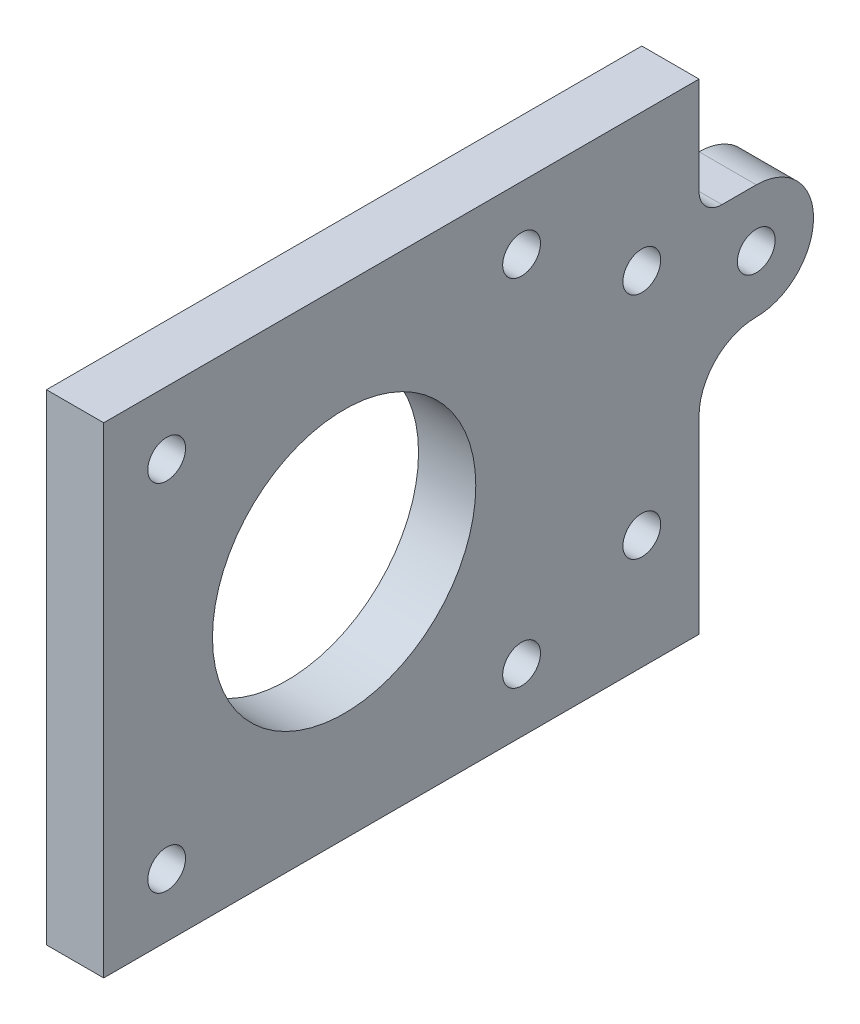
SolidWorks part; units mm, degrees
ref_plane "Front Plane" through (0, 0, 0) normal (0, 0, 1) x (1, 0, 0)
ref_plane "Top Plane" through (0, 0, 0) normal (0, 1, 0) x (1, 0, 0)
ref_plane "Right Plane" through (0, 0, 0) normal (1, 0, 0) x (0, 0, -1)
sketch "Sketch1" plane through (0, 0, 0) normal (1, 0, 0) x (0, 0, -1)
  line L1 (0, 0) -> (42, 0)
  line L2 (0, 0) -> (0, -42)
  line L3 (0, -42) -> (42, -42)
  line L4 (42, 0) -> (42, -42)
  dimension "D1" = 42
  dimension "D2" = 42
extrude "Boss-Extrude1" add sketch "Sketch1" along normal blind 5
sketch "Sketch2" plane through (5, 0, 0) normal (1, 0, 0) x (0, 0, -1)
  line L0 (42, 0) -> (0, 0) construction
  line L1 (0, 0) -> (0, -42) construction
  circle A0 centre (5.5, -5.5) radius 1.65
  circle A1 centre (36.5, -5.5) radius 1.65
  circle A2 centre (36.5, -36.5) radius 1.65
  circle A3 centre (5.5, -36.5) radius 1.65
  dimension "D1" = 3.3
  dimension "D2" = 5.5
  dimension "D3" = 5.5
  dimension "D4" = 2
  dimension "D5" = 2
extrude "Cut-Extrude1" cut sketch "Sketch2" against normal blind 5
sketch "Sketch3" plane through (0, 0, -42) normal (0, 0, -1) x (-1, 0, 0)
  line L1 (0, -42) -> (-5, -42)
  line L2 (0, -42) -> (0, 0)
  line L3 (0, 0) -> (-5, 0)
  line L4 (-5, -42) -> (-5, 0)
extrude "Boss-Extrude2" add sketch "Sketch3" along normal blind 10
sketch "Sketch4" plane through (0, 0, -52) normal (0, 0, -1) x (-1, 0, 0)
  line L0 (0, -42) -> (0, 0) construction
  line L1 (0, -20.5) -> (-5, -20.5)
  line L2 (0, -20.5) -> (0, -10.5)
  line L3 (0, -10.5) -> (-5, -10.5)
  line L4 (-5, -20.5) -> (-5, -10.5)
  line L5 (-5, 0) -> (-5, -42) construction
  dimension "D1" = 10
  dimension "D2" = 21.5
extrude "Boss-Extrude3" add sketch "Sketch4" along normal blind 10
sketch "Sketch5" plane through (5, 0, 0) normal (1, 0, 0) x (0, 0, -1)
  line L0 (52, -20.5) -> (52, -42) construction
  line L1 (52, 0) -> (52, -10.5) construction
  line L2 (0, -42) -> (52, -42) construction
  circle A0 centre (57, -15.5) radius 1.65
  circle A1 centre (47, -32) radius 1.65
  circle A2 centre (47, -12) radius 1.65
  dimension "D1" = 3.3
  dimension "D2" = 3.3
  dimension "D3" = 3.3
  dimension "D4" = 5
  dimension "D5" = 5
  dimension "D6" = 10
  dimension "D7" = 20
extrude "Cut-Extrude2" cut sketch "Sketch5" against normal blind 10
fillet "Fillet1" radius 5 3 edges at (2.5, -10.5, -62) (2.5, -20.5, -62) (2.5, -20.5, -52)
fillet "Fillet2" radius 2 1 edges at (2.5, -10.5, -52)
sketch "Sketch6" plane through (5, 0, 0) normal (1, 0, 0) x (0, 0, -1)
  line L0 (0, 0) -> (0, -42) construction
  line L1 (52, 0) -> (0, 0) construction
  circle A0 centre (21, -21) radius 11.5
  dimension "D1" = 23
  dimension "D2" = 21
  dimension "D3" = 21
extrude "Cut-Extrude3" cut sketch "Sketch6" against normal blind 10
equation "\"滑动-垂直孔\"= 0.6"
equation "\"滑动-水平孔\"= 0.3"
equation "\"松动-垂直孔\"= 0.3"
equation "\"松动-水平孔\"= 0.1"
equation "\"正常-垂直孔\"= 0.15"
equation "\"正常-水平孔\"= 0"
equation "\"紧缩-垂直孔\"= 0"
equation "\"紧缩-水平孔\"= - 0.1"
equation "\"D1@Sketch2\"=\"松动-垂直孔\"+3"
equation "\"D1@Sketch5\"=\"松动-垂直孔\"+3"
equation "\"D2@Sketch5\"=\"D1@Sketch5\""
equation "\"D3@Sketch5\"=\"D1@Sketch5\""
